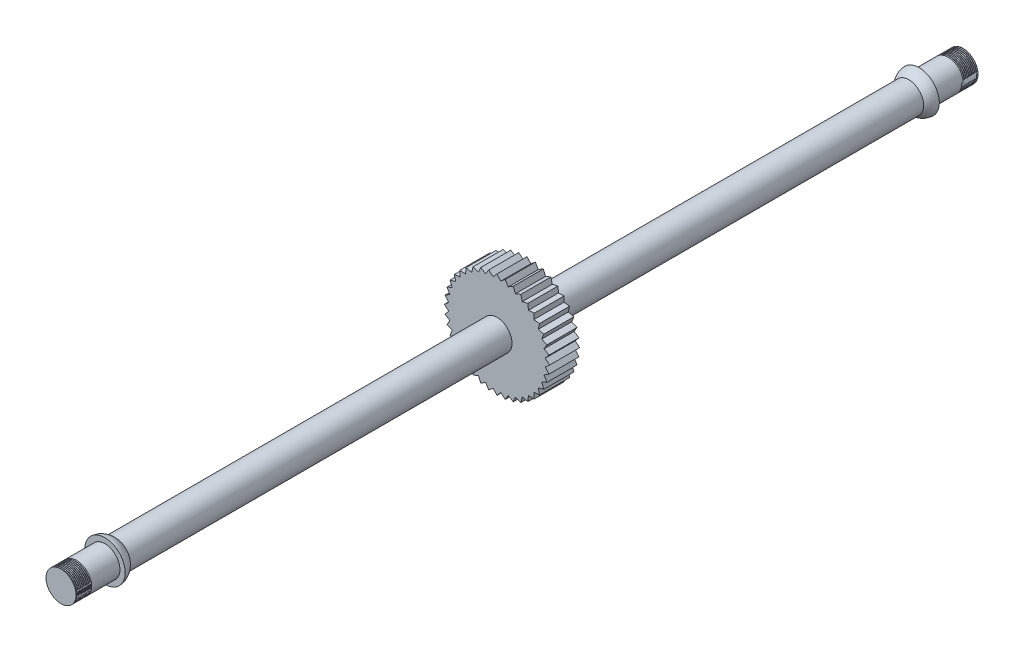
SolidWorks part; units mm, degrees
ref_plane "Front Plane" through (0, 0, 0) normal (0, 0, 1) x (1, 0, 0)
ref_plane "Top Plane" through (0, 0, 0) normal (0, 1, 0) x (1, 0, 0)
ref_plane "Right Plane" through (0, 0, 0) normal (1, 0, 0) x (0, 0, -1)
sketch "Sketch1" plane through (0, 0, 0) normal (0, 0, 1) x (1, 0, 0)
  circle A0 centre (0, 0) radius 12.7
  dimension "D1" = 25.4
extrude "Boss-Extrude1" add sketch "Sketch1" along normal mid plane 762
sketch "Sketch9" plane through (0, 0, 0) normal (0, 0, 1) x (1, 0, 0)
  line L0 (3.2093, 40.7782) -> (6.9535, 43.9027)
  line L3 (6.9535, 43.9027) -> (9.5489, 39.7741)
  line L7 (9.5489, 39.7741) -> (13.7358, 42.2745)
  line L9 (13.7358, 42.2745) -> (15.6534, 37.7906)
  line L12 (15.6534, 37.7906) -> (20.1799, 39.6052)
  line L13 (20.1799, 39.6052) -> (21.3724, 34.8766)
  line L16 (21.3724, 34.8766) -> (26.1271, 35.9608)
  line L17 (26.1271, 35.9608) -> (26.5652, 31.1039)
  line L20 (26.5652, 31.1039) -> (31.4309, 31.4309)
  line L21 (31.4309, 31.4309) -> (31.1039, 26.5652)
  line L24 (31.1039, 26.5652) -> (35.9608, 26.1271)
  line L25 (35.9608, 26.1271) -> (34.8766, 21.3724)
  line L28 (34.8766, 21.3724) -> (39.6052, 20.1799)
  line L29 (39.6052, 20.1799) -> (37.7906, 15.6534)
  line L32 (37.7906, 15.6534) -> (42.2745, 13.7358)
  line L33 (42.2745, 13.7358) -> (39.7741, 9.5489)
  line L36 (39.7741, 9.5489) -> (43.9027, 6.9535)
  line L37 (43.9027, 6.9535) -> (40.7782, 3.2093)
  line L40 (40.7782, 3.2093) -> (44.45, 0)
  line L41 (44.45, 0) -> (40.7782, -3.2093)
  line L44 (40.7782, -3.2093) -> (43.9027, -6.9535)
  line L45 (43.9027, -6.9535) -> (39.7741, -9.5489)
  line L48 (39.7741, -9.5489) -> (42.2745, -13.7358)
  line L49 (42.2745, -13.7358) -> (37.7906, -15.6534)
  line L52 (37.7906, -15.6534) -> (39.6052, -20.1799)
  line L53 (39.6052, -20.1799) -> (34.8766, -21.3724)
  line L56 (34.8766, -21.3724) -> (35.9608, -26.1271)
  line L57 (35.9608, -26.1271) -> (31.1039, -26.5652)
  line L60 (31.1039, -26.5652) -> (31.4309, -31.4309)
  line L61 (31.4309, -31.4309) -> (26.5652, -31.1039)
  line L64 (26.5652, -31.1039) -> (26.1271, -35.9608)
  line L65 (26.1271, -35.9608) -> (21.3724, -34.8766)
  line L68 (21.3724, -34.8766) -> (20.1799, -39.6052)
  line L69 (20.1799, -39.6052) -> (15.6534, -37.7906)
  line L72 (15.6534, -37.7906) -> (13.7358, -42.2745)
  line L73 (13.7358, -42.2745) -> (9.5489, -39.7741)
  line L76 (9.5489, -39.7741) -> (6.9535, -43.9027)
  line L77 (6.9535, -43.9027) -> (3.2093, -40.7782)
  line L80 (0, 44.45) -> (3.2093, 40.7782)
  line L100 (3.2093, -40.7782) -> (0, -44.45)
  line L119 (-3.2093, 40.7782) -> (0, 44.45)
  line L121 (0, -44.45) -> (-3.2093, -40.7782)
  line L123 (-3.2093, -40.7782) -> (-6.9535, -43.9027)
  line L124 (-6.9535, -43.9027) -> (-9.5489, -39.7741)
  line L126 (-9.5489, -39.7741) -> (-13.7358, -42.2745)
  line L127 (-13.7358, -42.2745) -> (-15.6534, -37.7906)
  line L129 (-15.6534, -37.7906) -> (-20.1799, -39.6052)
  line L130 (-20.1799, -39.6052) -> (-21.3724, -34.8766)
  line L132 (-21.3724, -34.8766) -> (-26.1271, -35.9608)
  line L133 (-26.1271, -35.9608) -> (-26.5652, -31.1039)
  line L135 (-26.5652, -31.1039) -> (-31.4309, -31.4309)
  line L136 (-31.4309, -31.4309) -> (-31.1039, -26.5652)
  line L138 (-31.1039, -26.5652) -> (-35.9608, -26.1271)
  line L139 (-35.9608, -26.1271) -> (-34.8766, -21.3724)
  line L148 (-34.8766, -21.3724) -> (-39.6052, -20.1799)
  line L161 (-39.6052, -20.1799) -> (-37.7906, -15.6534)
  line L177 (-37.7906, -15.6534) -> (-42.2745, -13.7358)
  line L178 (-42.2745, -13.7358) -> (-39.7741, -9.5489)
  line L180 (-39.7741, -9.5489) -> (-43.9027, -6.9535)
  line L181 (-43.9027, -6.9535) -> (-40.7782, -3.2093)
  line L183 (-40.7782, -3.2093) -> (-44.45, 0)
  line L184 (-44.45, 0) -> (-40.7782, 3.2093)
  line L186 (-40.7782, 3.2093) -> (-43.9027, 6.9535)
  line L187 (-43.9027, 6.9535) -> (-39.7741, 9.5489)
  line L189 (-39.7741, 9.5489) -> (-42.2745, 13.7358)
  line L190 (-42.2745, 13.7358) -> (-37.7906, 15.6534)
  line L192 (-37.7906, 15.6534) -> (-39.6052, 20.1799)
  line L193 (-39.6052, 20.1799) -> (-34.8766, 21.3724)
  line L195 (-34.8766, 21.3724) -> (-35.9608, 26.1271)
  line L196 (-35.9608, 26.1271) -> (-31.1039, 26.5652)
  line L198 (-31.1039, 26.5652) -> (-31.4309, 31.4309)
  line L199 (-31.4309, 31.4309) -> (-26.5652, 31.1039)
  line L201 (-26.5652, 31.1039) -> (-26.1271, 35.9608)
  line L202 (-26.1271, 35.9608) -> (-21.3724, 34.8766)
  line L204 (-21.3724, 34.8766) -> (-20.1799, 39.6052)
  line L205 (-20.1799, 39.6052) -> (-15.6534, 37.7906)
  line L207 (-15.6534, 37.7906) -> (-13.7358, 42.2745)
  line L208 (-13.7358, 42.2745) -> (-9.5489, 39.7741)
  line L210 (-9.5489, 39.7741) -> (-6.9535, 43.9027)
  line L211 (-6.9535, 43.9027) -> (-3.2093, 40.7782)
  point P85 (0, 0)
  point P124 (0, 0)
  point P149 (0, 0)
  dimension "D1" = 40
  dimension "D2" = 3.2093
  dimension "D3" = 6.9535
  dimension "D4" = 4.8767
  dimension "D5" = 82.31
  dimension "D6" = 44.45
  dimension "D7" = 40.9043
  dimension "D8" = 40.7782
extrude "Boss-Extrude3" add sketch "Sketch9" along normal mid plane 25.4
thread "Thread1" pitch 1.27 method cut profile "Thread Profile1" start angle 0, offset 0, length 12.7, pitch 1.27, diameter 25.4
ref_plane "Plane1" through (-12.7, 0, 381) normal (0, -1, 0) x (-1, 0, 0)
sketch "Thread Profile1" plane through (-12.7, 0, 381) normal (0, -1, 0) x (-1, 0, 0)
  line L0 (0, 0) -> (0, 1.27) construction
  line L11 (0, 0) -> (0, 1.1112)
  line L12 (0, 1.1112) -> (-0.6874, 0.7144)
  line L13 (-0.6874, 0.7144) -> (-0.6874, 0.3969)
  line L15 (-0.6874, 0.3969) -> (0, 0)
  line L17 (-0.6874, 0.5556) -> (0, 0.5556) construction
  point P2 (0, 0)
  dimension "Pitch" = 1.27
  dimension "Profile_Angle" = 60
  dimension "Profile_Land" = 0.3175
  dimension "Profile_Height" = 0.6874
thread "Thread2" pitch 1.27 method cut profile "Thread Profile2" start angle 0, offset 0, length 12.7, pitch 1.27, diameter 25.4
ref_plane "Plane2" through (12.7, 0, -381) normal (0, -1, 0) x (1, 0, 0)
sketch "Thread Profile2" plane through (12.7, 0, -381) normal (0, -1, 0) x (1, 0, 0)
  line L0 (0, 0) -> (0, 1.27) construction
  line L11 (0, 0) -> (0, 1.1112)
  line L12 (0, 1.1112) -> (-0.6874, 0.7144)
  line L13 (-0.6874, 0.7144) -> (-0.6874, 0.3969)
  line L15 (-0.6874, 0.3969) -> (0, 0)
  line L17 (-0.6874, 0.5556) -> (0, 0.5556) construction
  point P2 (0, 0)
  dimension "Pitch" = 1.27
  dimension "Profile_Angle" = 60
  dimension "Profile_Land" = 0.3175
  dimension "Profile_Height" = 0.6874
sketch "Sketch11" plane through (0, 0, 0) normal (0, 1, 0) x (1, 0, 0)
  line L1 (17.0962, 343.9201) -> (12.7, 343.9201)
  line L2 (12.7, 343.9201) -> (12.7, 335.1278)
  arc A0 (17.0962, 343.9201) -> (12.7, 335.1278) centre (4.6407, 344.6526) cw
  dimension "D1" = 12.477
  dimension "D2" = 4.6407
  dimension "D3" = 12.7
  dimension "D4" = 17.0962
  dimension "D5" = 335.1278
sketch "Sketch12" plane through (0, 0, 0) normal (0, 1, 0) x (1, 0, 0)
  line L0 (0, 0) -> (0, 172.9119)
  dimension "D1" = 172.9119
revolve "Revolve1" add sketch "Sketch11" angle 360 about L0
mirror "Mirror1" about plane through (0, 0, 0) normal (0, 0, 1) of "Revolve1"
